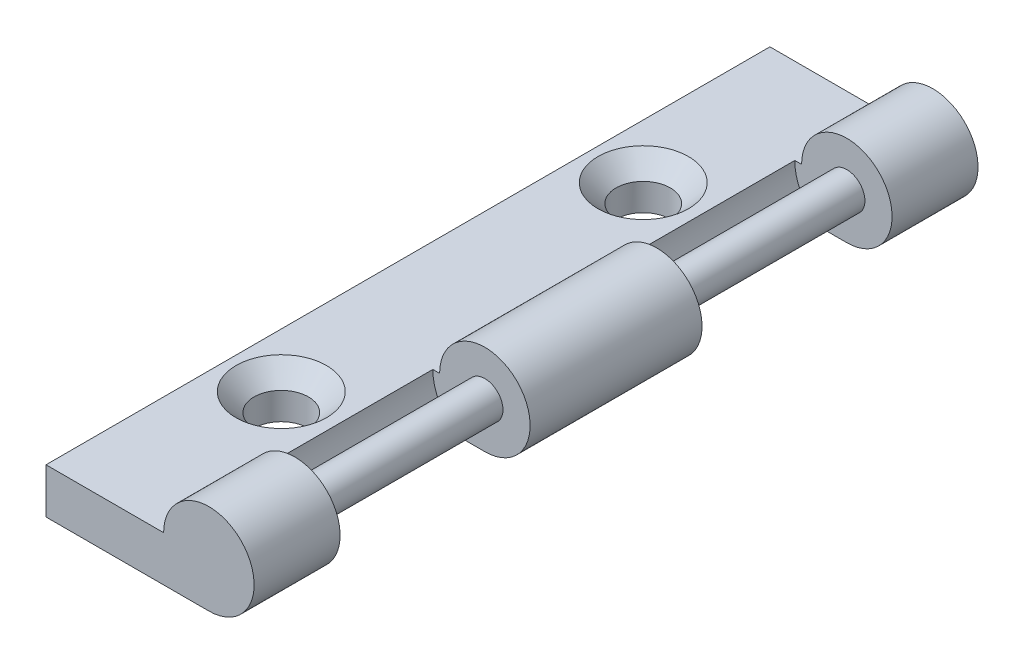
SolidWorks part; units mm, degrees
ref_plane "Front Plane" through (0, 0, 0) normal (0, 0, 1) x (1, 0, 0)
ref_plane "Top Plane" through (0, 0, 0) normal (0, 1, 0) x (1, 0, 0)
ref_plane "Right Plane" through (0, 0, 0) normal (1, 0, 0) x (0, 0, -1)
sketch "Sketch1" plane through (0, 0, 0) normal (0, 1, 0) x (1, 0, 0)
  line L1 (-9, 40) -> (0, 40)
  line L2 (-9, 40) -> (-9, 0)
  line L3 (-9, 0) -> (0, 0)
  line L4 (0, 40) -> (0, 0)
  dimension "D1" = 40
  dimension "D2" = 9
extrude "Boss-Extrude1" add sketch "Sketch1" along normal blind 2.5
sketch "Sketch2" plane through (0, 0, 0) normal (0, 0, 1) x (1, 0, 0)
  circle A0 centre (0, 2.5) radius 2.5
extrude "Boss-Extrude2" add sketch "Sketch2" against normal up to surface (40 mm away) up to face at (-4.5, 1.25, -40)
sketch "Sketch3" plane through (0, 0, 0) normal (0, 0, 1) x (1, 0, 0)
  circle A1 centre (0, 2.5) radius 2.875
  dimension "D1" = 5.75
extrude "Cut-Extrude1" cut sketch "Sketch3" against normal blind 10.5 from offset 4.75 offset against normal yes
ref_plane "Plane1" through (0, 0, -20) normal (0, 0, 1) x (1, 0, 0)
mirror "Mirror1" about plane through (0, 0, -20) normal (0, 0, 1) of "Cut-Extrude1"
sketch "Sketch4" plane through (0, 0, -15.25) normal (0, 0, 1) x (1, 0, 0)
  circle A0 centre (0, 2.5) radius 1
  dimension "D1" = 2
extrude "Boss-Extrude3" add sketch "Sketch4" along normal up to next
mirror "Mirror2" about plane through (0, 0, -20) normal (0, 0, 1) of "Boss-Extrude3"
sketch "Sketch5" plane through (0, 2.5, 0) normal (0, 1, 0) x (1, 0, 0)
  line L0 (-9, 0) -> (-2.5, 0) construction
  line L1 (-9, 40) -> (-9, 0) construction
  circle A0 centre (-6, 10) radius 1.5
  dimension "D1" = 3
  dimension "D2" = 10
  dimension "D3" = 3
extrude "Cut-Extrude2" cut sketch "Sketch5" against normal through all
mirror "Mirror3" about plane through (0, 0, -20) normal (0, 0, 1) of "Cut-Extrude2"
chamfer "Chamfer1" distance 1 angle 45 1 edges at (-6, 2.5, -8.5)
chamfer "Chamfer2" distance 1 angle 45 1 edges at (-6, 2.5, -31.5)
